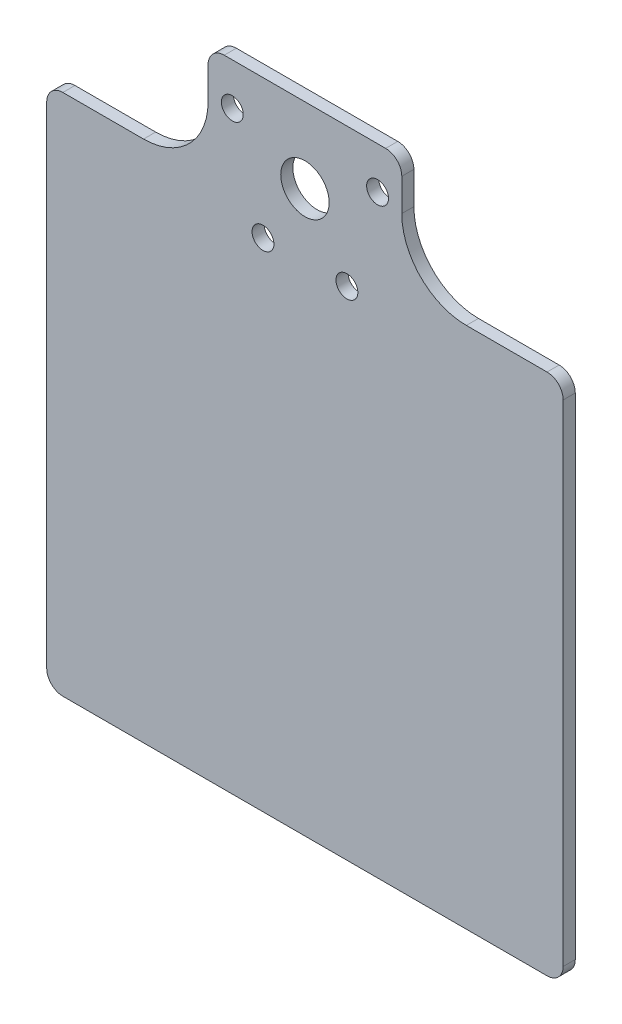
SolidWorks part; units mm, degrees
material "PC High Viscosity"
ref_plane "Front Plane" through (0, 0, 0) normal (0, 0, 1) x (1, 0, 0)
ref_plane "Top Plane" through (0, 0, 0) normal (0, 1, 0) x (1, 0, 0)
ref_plane "Right Plane" through (0, 0, 0) normal (1, 0, 0) x (0, 0, -1)
sketch "Sketch1" plane through (0, 0, 0) normal (0, 0, 1) x (1, 0, 0)
  line L1 (-19.05, -17.4625) -> (19.05, -17.4625)
  line L2 (-19.05, -17.4625) -> (-19.05, 17.4625)
  line L3 (-19.05, 17.4625) -> (19.05, 17.4625)
  line L4 (19.05, -17.4625) -> (19.05, 17.4625)
  line L5 (-19.05, -17.4625) -> (19.05, 17.4625) construction
  line L6 (-19.05, 17.4625) -> (19.05, -17.4625) construction
  point P0 (0, 0)
  dimension "D1" = 38.1
  dimension "D2" = 34.925
extrude "Boss-Extrude1" add sketch "Sketch1" along normal blind 2.3813
sketch "Sketch5" plane through (0, 0, 2.3813) normal (0, 0, 1) x (1, 0, 0)
  line L0 (-19.05, -17.4625) -> (19.05, -17.4625) construction
  line L1 (-50.8, -107.6325) -> (50.8, -107.6325)
  line L2 (-50.8, -107.6325) -> (-50.8, -17.4625)
  line L3 (-50.8, -17.4625) -> (50.8, -17.4625)
  line L4 (50.8, -107.6325) -> (50.8, -17.4625)
  line L5 (-50.8, -107.6325) -> (50.8, -17.4625) construction
  line L6 (-50.8, -17.4625) -> (50.8, -107.6325) construction
  point P0 (0, -62.5475)
  dimension "D1" = 101.6
  dimension "D2" = 90.17
extrude "Boss-Extrude2" add sketch "Sketch5" against normal up to surface (2.3813 mm away) up to face at (0, 0, 0)
sketch "Sketch6" plane through (0, 0, 0) normal (0, 0, -1) x (-1, 0, 0)
  line L0 (19.05, -17.4625) -> (50.8, -17.4625) construction
  circle A0 centre (0, 2.6543) radius 4.7625
  dimension "D1" = 9.525
  dimension "D2" = 20.1168
extrude "Cut-Extrude2" cut sketch "Sketch6" against normal up to next
hole_wizard "#8 Clearance Hole1" positions "Sketch9" profile "Sketch8" hole size "#8" standard "Ansi Inch"
sketch "Sketch9" plane through (0, 0, 0) normal (0, 0, -1) x (-1, 0, 0)
  line L0 (-50.8, -17.4625) -> (-19.05, -17.4625) construction
  point P0 (-8.255, -9.8425)
  point P1 (8.255, -9.8425)
  point P3 (-14.2875, 9.2075)
  point P5 (14.2875, 9.2075)
  dimension "D1" = 16.51
  dimension "D2" = 8.255
  dimension "D3" = 7.62
  dimension "D4" = 19.05
  dimension "D5" = 28.575
  dimension "D6" = 14.2875
sketch "Sketch8" plane through (8.255, -9.8425, 0) normal (1, 0, 0) x (0, 1, 0)
  line L0 (0, 0) -> (0, 13.9934)
  line L1 (0, 13.9934) -> (2.1526, 12.7)
  line L2 (2.1526, 12.7) -> (2.1526, 0)
  line L5 (2.1526, 0) -> (0, 0)
  line L10 (0, 13.9934) -> (-2.1527, 12.7) construction
  line L11 (0, -6.35) -> (0, 107.95) construction
  dimension "Hole Dia." = 4.3053
  dimension "Hole Depth" = 12.7
  dimension "Drill Angle" = 118
sketch "Sketch11" plane through (0, 0, 2.3813) normal (0, 0, 1) x (1, 0, 0)
  line L0 (-19.05, 17.4625) -> (-19.05, -17.4625) construction
  line L1 (-50.8, -17.4625) -> (-19.05, -17.4625)
  line L2 (-50.8, -17.4625) -> (-50.8, -4.7625)
  line L3 (-50.8, -4.7625) -> (-19.05, -4.7625)
  line L4 (-19.05, -17.4625) -> (-19.05, -4.7625)
  line L5 (19.05, -17.4625) -> (19.05, 17.4625) construction
  line L6 (50.8, -17.4625) -> (19.05, -17.4625)
  line L7 (50.8, -17.4625) -> (50.8, -4.7625)
  line L8 (50.8, -4.7625) -> (19.05, -4.7625)
  line L9 (19.05, -17.4625) -> (19.05, -4.7625)
  dimension "D1" = 12.7
extrude "Boss-Extrude3" add sketch "Sketch11" against normal up to surface (2.3813 mm away) up to face at (6.1024, -9.8425, 0)
fillet "Fillet3" radius 3.175 6 edges at (-50.8, -107.6325, 1.1906) (50.8, -107.6325, 1.1906) (-19.05, 17.4625, 1.1906) (19.05, 17.4625, 1.1906) (50.8, -4.7625, 1.1906) (-50.8, -4.7625, 1.1906)
fillet "Fillet4" radius 12.7 2 edges at (19.05, -4.7625, 1.1906) (-19.05, -4.7625, 1.1906)
